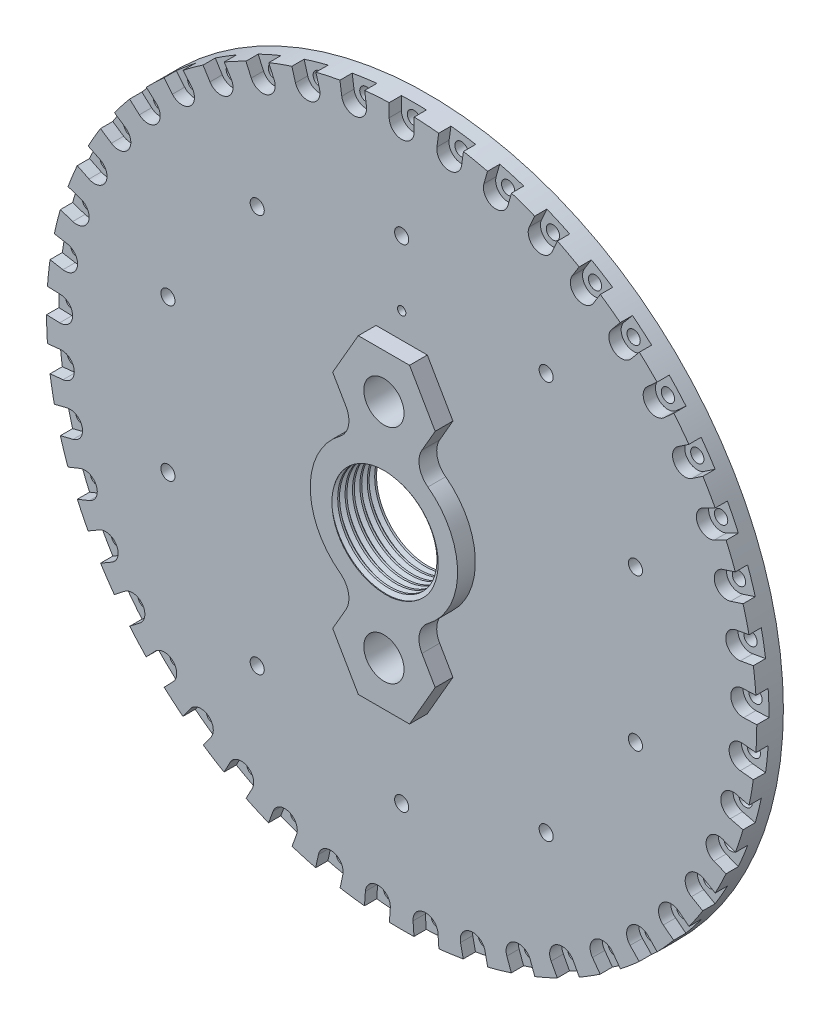
SolidWorks part; units mm, degrees
material "AISI 316 Stainless Steel Sheet (SS)"
ref_plane "Front Plane" through (0, 0, 0) normal (0, 0, 1) x (1, 0, 0)
ref_plane "Top Plane" through (0, 0, 0) normal (0, 1, 0) x (1, 0, 0)
ref_plane "Right Plane" through (0, 0, 0) normal (1, 0, 0) x (0, 0, -1)
sketch "Sketch1" plane through (0, 0, 0) normal (1, 0, 0) x (0, 0, -1)
  line L0 (0, 21.082) -> (0, 101.6)
  line L1 (0, 101.6) -> (7.62, 101.6)
  line L2 (7.62, 101.6) -> (7.62, 88.6333)
  line L3 (7.62, 83.82) -> (5.08, 83.82)
  line L4 (5.08, 83.82) -> (5.08, 56.8325)
  line L5 (5.08, 56.8325) -> (7.62, 56.8325)
  line L6 (7.62, 56.8325) -> (7.62, 53.0225)
  line L7 (7.62, 14.732) -> (-5.08, 14.732)
  line L8 (-5.08, 14.732) -> (-5.08, 21.082)
  line L9 (-5.08, 21.082) -> (0, 21.082)
  line L10 (0, 0) -> (59.2702, 0) construction
  line L12 (7.62, 49.6951) -> (6.2992, 49.6951)
  line L14 (7.62, 47.0535) -> (6.2992, 47.0535)
  line L15 (6.2992, 49.6951) -> (6.2992, 47.0535)
  line L20 (7.62, 47.0535) -> (7.62, 46.0375)
  line L21 (7.62, 85.1027) -> (7.62, 83.82)
  line L22 (7.62, 50.4825) -> (7.62, 49.6951)
  line L23 (7.62, 21.59) -> (7.62, 14.732)
  line L24 (7.62, 46.0375) -> (5.08, 46.0375)
  line L26 (7.62, 21.59) -> (5.08, 21.59)
  line L27 (5.08, 46.0375) -> (5.08, 21.59)
  line L28 (7.62, 53.0225) -> (6.35, 53.0225)
  line L32 (7.62, 50.4825) -> (6.35, 50.4825)
  line L33 (6.35, 53.0225) -> (6.35, 50.4825)
  line L35 (7.62, 88.6333) -> (5.6642, 88.6333)
  line L37 (7.62, 85.1027) -> (5.6642, 85.1027)
  line L38 (5.6642, 88.6333) -> (5.6642, 85.1027)
  point P19 (6.35, 51.7525)
  point P22 (6.2992, 48.3743)
  point P31 (5.6642, 86.868)
  dimension "D1" = 203.2
  dimension "D6" = 12.7
  dimension "D8" = 6.35
  dimension "D10" = 96.7486
  dimension "D9" = 2.6416
  dimension "D11" = 1.3208
  dimension "D7" = 29.464
  dimension "D4" = 2.54
  dimension "D14" = 43.18
  dimension "D2" = 2.54
  dimension "D3" = 7.62
  dimension "D12" = 167.64
  dimension "D5" = 113.665
  dimension "D13" = 92.075
  dimension "D15" = 1.27
  dimension "D16" = 2.54
  dimension "D17" = 103.505
  dimension "D18" = 1.9558
  dimension "D19" = 3.5306
  dimension "D20" = 173.736
revolve "Revolve1" add sketch "Sketch1" angle 360 about L10 region at (0, 56.7778, -2.7599)
thread "Thread1" pitch 2.1167 method cut profile "Thread Profile1" start angle 0, offset 4.318, length 0, pitch 2.1167, diameter 29.464
ref_plane "Plane1" through (-14.732, 0, 9.398) normal (0, -1, 0) x (-1, 0, 0)
sketch "Thread Profile1" plane through (-14.732, 0, 9.398) normal (0, -1, 0) x (-1, 0, 0)
  line L0 (0, 0) -> (0, 2.1167) construction
  line L1 (0, 0) -> (1.1457, 0.6615)
  line L2 (1.1457, 0.6615) -> (1.1457, 0.926)
  line L3 (1.1457, 0.926) -> (0, 1.5875)
  line L4 (1.1457, 0.7937) -> (0, 0.7937) construction
  line L11 (0, 0) -> (0, 1.5875)
  point P2 (0, 0)
  dimension "Pitch" = 2.1167
  dimension "Profile_Angle" = 60
  dimension "Profile_Land" = 0.2646
  dimension "Profile_Height" = 1.1457
sketch "Sketch15" plane through (0, 0, 0) normal (0, 0, 1) x (1, 0, 0)
  line L10 (0, 0) -> (104.8126, 0) construction
  line L11 (7.3323, 19.05) -> (14.6647, 31.75)
  line L12 (14.6647, 31.75) -> (7.3323, 44.45)
  line L13 (7.3323, 44.45) -> (-7.3323, 44.45)
  line L14 (-7.3323, 44.45) -> (-14.6647, 31.75)
  line L15 (-14.6647, 31.75) -> (-7.3323, 19.05)
  line L16 (-7.3323, 19.05) -> (7.3323, 19.05)
  line L17 (-7.3323, -19.05) -> (7.3323, -19.05)
  line L18 (-14.6647, -31.75) -> (-7.3323, -19.05)
  line L19 (-7.3323, -44.45) -> (-14.6647, -31.75)
  line L20 (7.3323, -44.45) -> (-7.3323, -44.45)
  line L21 (14.6647, -31.75) -> (7.3323, -44.45)
  line L22 (7.3323, -19.05) -> (14.6647, -31.75)
  circle A8 centre (0, 31.75) radius 12.7 construction
  circle A9 centre (0, -31.75) radius 12.7 construction
  dimension "D2" = 63.5
  dimension "D1" = 25.4
extrude "Boss-Extrude1" add sketch "Sketch15" along normal up to surface (5.08 mm away) up to face at (21.082, 0, 5.08)
hole_wizard "1/2-20 Tapped Hole2" positions "Sketch20" profile "Sketch17" tap size "1/2-20" standard "ANSI Inch" end condition through all
sketch "Sketch20" plane through (0, 0, 5.08) normal (0, 0, 1) x (1, 0, 0)
  point P9 (0, 31.75)
  point P16 (0, -31.75)
sketch "Sketch17" plane through (0, 31.75, 5.08) normal (1, 0, 0) x (0, -1, 0)
  line L0 (0, 0) -> (0, 13.4424)
  line L1 (0, 13.4424) -> (5.7544, 13.4424)
  line L2 (5.7544, 13.4424) -> (5.7544, 0)
  line L5 (5.7544, 0) -> (0, 0)
  line L11 (0, -6.35) -> (0, 107.95) construction
  dimension "Thru Tap Drill Dia." = 11.5087
  dimension "Thru Tap Drill Depth" = 13.4424
cosmetic thread "Hole Thread3" parameters "D2"=12.7
cosmetic thread "Hole Thread4" parameters "D2"=12.7
hole_wizard "CBORE for #6 Socket Head Cap Screw1" positions "Sketch31" profile "Sketch9" counterbore size "#6" standard "ANSI Inch" end condition up to next
sketch "Sketch31" [suppressed] plane through (0, 0, 0) normal (0, 0, 1) x (1, 0, 0)
  circle A0 centre (0, 0) radius 97.79 construction
  point P0 (0, 97.79)
  point P16 (13.6097, 96.8383)
  point P17 (26.9546, 94.0018)
  point P18 (39.7748, 89.3356)
  point P19 (51.8208, 82.9306)
  point P20 (62.8582, 74.9115)
  point P21 (72.6721, 65.4343)
  point P22 (81.0716, 54.6835)
  point P23 (87.8931, 42.8683)
  point P24 (93.0038, 30.2188)
  point P25 (96.3044, 16.9811)
  point P26 (97.7304, 3.4128)
  point P27 (97.2543, -10.2218)
  point P28 (94.8852, -23.6575)
  point P29 (90.6693, -36.6328)
  point P30 (84.6886, -48.895)
  point P31 (77.0596, -60.2055)
  point P32 (67.9306, -70.3442)
  point P33 (57.4795, -79.1138)
  point P34 (45.9096, -86.3434)
  point P35 (33.4461, -91.8925)
  point P36 (20.3317, -95.6531)
  point P37 (6.8215, -97.5518)
  point P38 (-6.8215, -97.5518)
  point P39 (-20.3317, -95.6531)
  point P40 (-33.4461, -91.8925)
  point P41 (-45.9096, -86.3434)
  point P42 (-57.4795, -79.1138)
  point P43 (-67.9306, -70.3442)
  point P44 (-77.0596, -60.2055)
  point P45 (-84.6886, -48.895)
  point P46 (-90.6693, -36.6328)
  point P47 (-94.8852, -23.6575)
  point P48 (-97.2543, -10.2218)
  point P49 (-97.7304, 3.4128)
  point P50 (-96.3044, 16.9811)
  point P51 (-93.0038, 30.2188)
  point P52 (-87.8931, 42.8683)
  point P53 (-81.0716, 54.6835)
  point P54 (-72.6721, 65.4343)
  point P55 (-62.8582, 74.9115)
  point P56 (-51.8208, 82.9306)
  point P57 (-39.7748, 89.3356)
  point P58 (-26.9546, 94.0018)
  point P59 (-13.6097, 96.8383)
  dimension "D1" = 195.58
  dimension "D2" = 45
sketch "Sketch9" plane through (0, 97.79, 0) normal (1, 0, 0) x (0, -1, 0)
  line L0 (0, 0) -> (0, 7.62)
  line L1 (0, 7.62) -> (1.8986, 7.62)
  line L3 (1.8986, 7.62) -> (1.8986, 3.5052)
  line L4 (1.8986, 3.5052) -> (3.5725, 3.5052)
  line L5 (3.5725, 3.5052) -> (3.5725, 0)
  line L7 (3.5725, 0) -> (0, 0)
  line L11 (0, -6.35) -> (0, 107.95) construction
  dimension "Thru Hole Dia." = 3.7973
  dimension "Thru Hole Depth" = 7.62
  dimension "C'Bore Dia." = 7.145
  dimension "C'Bore Depth" = 3.5052
sketch "Sketch29" plane through (0, 0, 0) normal (0, 0, 1) x (1, 0, 0)
  line L0 (3.5725, 97.79) -> (3.5725, 101.5372)
  line L1 (-3.5725, 97.79) -> (-3.5725, 101.5372)
  line L2 (17.1475, 96.3411) -> (17.669, 100.0518)
  line L3 (10.072, 97.3355) -> (10.5935, 101.0462)
  line L4 (30.3887, 93.0171) -> (31.4216, 96.6191)
  line L5 (23.5205, 94.9865) -> (24.5533, 98.5885)
  line L6 (43.0384, 87.8825) -> (44.5625, 91.3058)
  line L7 (36.5111, 90.7887) -> (38.0352, 94.2119)
  line L8 (54.8505, 81.0375) -> (56.8362, 84.2153)
  line L9 (48.7911, 84.8238) -> (50.7768, 88.0015)
  line L10 (65.5949, 72.6151) -> (68.0035, 75.4856)
  line L11 (60.1215, 77.2079) -> (62.5301, 80.0784)
  line L12 (75.0626, 62.7794) -> (77.8473, 65.2867)
  line L13 (70.2817, 68.0892) -> (73.0663, 70.5965)
  line L14 (83.0693, 51.7217) -> (86.1759, 53.8171)
  line L15 (79.0739, 57.6452) -> (82.1804, 59.7406)
  line L16 (89.4592, 39.6574) -> (92.8271, 41.3)
  line L17 (86.327, 46.0793) -> (89.6949, 47.7219)
  line L18 (94.1078, 26.8211) -> (97.6716, 27.9791)
  line L19 (91.8999, 33.6164) -> (95.4636, 34.7744)
  line L20 (96.9247, 13.4628) -> (100.615, 14.1135)
  line L21 (95.684, 20.4993) -> (99.3742, 21.15)
  line L22 (97.8551, -0.1575) -> (101.6, -0.0267)
  line L23 (97.6058, 6.9832) -> (101.3506, 7.1139)
  line L24 (96.8809, -13.7748) -> (100.6075, -14.1665)
  line L25 (97.6277, -6.6689) -> (101.3544, -7.0606)
  line L26 (94.021, -27.1239) -> (97.6568, -28.0305)
  line L27 (95.7495, -20.1912) -> (99.3854, -21.0977)
  line L28 (89.331, -39.9452) -> (92.8053, -41.3489)
  line L29 (92.0076, -33.3204) -> (95.4819, -34.7241)
  line L30 (82.9024, -51.9889) -> (86.1475, -53.8625)
  line L31 (86.4749, -45.8011) -> (89.72, -47.6747)
  line L32 (74.8601, -63.0207) -> (77.8129, -65.3277)
  line L33 (79.259, -57.3904) -> (82.2118, -59.6973)
  line L34 (65.3608, -72.8259) -> (67.9638, -75.5214)
  line L35 (70.5005, -67.8626) -> (73.1035, -70.5581)
  line L36 (54.5893, -81.2136) -> (56.7918, -84.2452)
  line L37 (60.3697, -77.0139) -> (62.5723, -80.0454)
  line L38 (42.7553, -88.0206) -> (44.5145, -91.3292)
  line L39 (49.064, -84.6663) -> (50.8232, -87.9748)
  line L40 (30.0891, -93.1144) -> (31.3707, -96.6356)
  line L41 (36.8032, -90.6707) -> (38.0848, -94.1919)
  line L42 (16.8372, -96.3958) -> (17.6163, -100.0611)
  line L43 (23.8261, -94.9103) -> (24.6052, -98.5756)
  line L44 (3.2577, -97.801) -> (3.5191, -101.539)
  line L45 (10.3853, -97.3026) -> (10.6467, -101.0406)
  line L46 (-10.3853, -97.3026) -> (-10.6467, -101.0406)
  line L47 (-3.2577, -97.801) -> (-3.5191, -101.539)
  line L48 (-23.8261, -94.9103) -> (-24.6052, -98.5756)
  line L49 (-16.8372, -96.3958) -> (-17.6163, -100.0611)
  line L50 (-36.8032, -90.6707) -> (-38.0848, -94.1919)
  line L51 (-30.0891, -93.1144) -> (-31.3707, -96.6356)
  line L52 (-49.064, -84.6663) -> (-50.8232, -87.9748)
  line L53 (-42.7553, -88.0206) -> (-44.5145, -91.3292)
  line L54 (-60.3697, -77.0139) -> (-62.5723, -80.0454)
  line L55 (-54.5893, -81.2136) -> (-56.7918, -84.2452)
  line L56 (-70.5005, -67.8626) -> (-73.1035, -70.5581)
  line L57 (-65.3608, -72.8259) -> (-67.9638, -75.5214)
  line L58 (-79.259, -57.3904) -> (-82.2118, -59.6973)
  line L59 (-74.8601, -63.0207) -> (-77.8129, -65.3277)
  line L60 (-86.4749, -45.8011) -> (-89.72, -47.6747)
  line L61 (-82.9024, -51.9889) -> (-86.1475, -53.8625)
  line L62 (-92.0076, -33.3204) -> (-95.4819, -34.7241)
  line L63 (-89.331, -39.9452) -> (-92.8053, -41.3489)
  line L64 (-95.7495, -20.1912) -> (-99.3854, -21.0977)
  line L65 (-94.021, -27.1239) -> (-97.6568, -28.0305)
  line L66 (-97.6277, -6.6689) -> (-101.3544, -7.0606)
  line L67 (-96.8809, -13.7748) -> (-100.6075, -14.1665)
  line L68 (-97.6058, 6.9832) -> (-101.3506, 7.1139)
  line L69 (-97.8551, -0.1575) -> (-101.6, -0.0267)
  line L70 (-95.684, 20.4993) -> (-99.3742, 21.15)
  line L71 (-96.9247, 13.4628) -> (-100.615, 14.1135)
  line L72 (-91.8999, 33.6164) -> (-95.4636, 34.7744)
  line L73 (-94.1078, 26.8211) -> (-97.6716, 27.9791)
  line L74 (-86.327, 46.0793) -> (-89.6949, 47.7219)
  line L75 (-89.4592, 39.6574) -> (-92.8271, 41.3)
  line L76 (-79.0739, 57.6452) -> (-82.1804, 59.7406)
  line L77 (-83.0693, 51.7217) -> (-86.1759, 53.8171)
  line L78 (-70.2817, 68.0892) -> (-73.0663, 70.5965)
  line L79 (-75.0626, 62.7794) -> (-77.8473, 65.2867)
  line L80 (-60.1215, 77.2079) -> (-62.5301, 80.0784)
  line L81 (-65.5949, 72.6151) -> (-68.0035, 75.4856)
  line L82 (-48.7911, 84.8238) -> (-50.7768, 88.0015)
  line L83 (-54.8505, 81.0375) -> (-56.8362, 84.2153)
  line L84 (-36.5111, 90.7887) -> (-38.0352, 94.2119)
  line L85 (-43.0384, 87.8825) -> (-44.5625, 91.3058)
  line L86 (-23.5205, 94.9865) -> (-24.5533, 98.5885)
  line L87 (-30.3887, 93.0171) -> (-31.4216, 96.6191)
  line L88 (-10.072, 97.3355) -> (-10.5935, 101.0462)
  line L89 (-17.1475, 96.3411) -> (-17.669, 100.0518)
  circle A0 centre (0, 97.79) radius 3.5725 construction
  circle A1 centre (0, 0) radius 101.6 construction
  circle A2 centre (13.6097, 96.8383) radius 3.5725
  circle A3 centre (0, 97.79) radius 3.5725
  circle A4 centre (26.9546, 94.0018) radius 3.5725
  circle A5 centre (0, 0) radius 101.6
  circle A7 centre (39.7748, 89.3356) radius 3.5725
  circle A8 centre (51.8208, 82.9306) radius 3.5725
  circle A9 centre (62.8582, 74.9115) radius 3.5725
  circle A10 centre (72.6721, 65.4343) radius 3.5725
  circle A11 centre (81.0716, 54.6835) radius 3.5725
  circle A12 centre (87.8931, 42.8683) radius 3.5725
  circle A13 centre (93.0038, 30.2188) radius 3.5725
  circle A14 centre (96.3044, 16.9811) radius 3.5725
  circle A15 centre (97.7304, 3.4128) radius 3.5725
  circle A16 centre (97.2543, -10.2218) radius 3.5725
  circle A17 centre (94.8852, -23.6575) radius 3.5725
  circle A18 centre (90.6693, -36.6328) radius 3.5725
  circle A19 centre (84.6886, -48.895) radius 3.5725
  circle A20 centre (77.0596, -60.2055) radius 3.5725
  circle A21 centre (67.9306, -70.3442) radius 3.5725
  circle A22 centre (57.4795, -79.1138) radius 3.5725
  circle A23 centre (45.9096, -86.3434) radius 3.5725
  circle A24 centre (33.4461, -91.8925) radius 3.5725
  circle A25 centre (13.6097, 96.8383) radius 1.8986 construction
  circle A26 centre (20.3317, -95.6531) radius 3.5725
  circle A27 centre (6.8215, -97.5518) radius 3.5725
  circle A28 centre (-6.8215, -97.5518) radius 3.5725
  circle A29 centre (-20.3317, -95.6531) radius 3.5725
  circle A30 centre (-33.4461, -91.8925) radius 3.5725
  circle A31 centre (-45.9096, -86.3434) radius 3.5725
  circle A32 centre (-57.4795, -79.1138) radius 3.5725
  circle A33 centre (-67.9306, -70.3442) radius 3.5725
  circle A34 centre (-77.0596, -60.2055) radius 3.5725
  circle A35 centre (-84.6886, -48.895) radius 3.5725
  circle A36 centre (-90.6693, -36.6328) radius 3.5725
  circle A37 centre (-94.8852, -23.6575) radius 3.5725
  circle A38 centre (-97.2543, -10.2218) radius 3.5725
  circle A39 centre (-97.7304, 3.4128) radius 3.5725
  circle A40 centre (-96.3044, 16.9811) radius 3.5725
  circle A41 centre (-93.0038, 30.2188) radius 3.5725
  circle A42 centre (-87.8931, 42.8683) radius 3.5725
  circle A43 centre (-81.0716, 54.6835) radius 3.5725
  circle A44 centre (-72.6721, 65.4343) radius 3.5725
  circle A45 centre (-62.8582, 74.9115) radius 3.5725
  circle A46 centre (-51.8208, 82.9306) radius 3.5725
  circle A47 centre (-39.7748, 89.3356) radius 3.5725
  circle A48 centre (-26.9546, 94.0018) radius 3.5725
  circle A49 centre (-13.6097, 96.8383) radius 3.5725
  circle A51 centre (0, 0) radius 101.6
  point P129 (0, 0)
  dimension "D2" = 45
extrude "Cut-Extrude1" cut sketch "Sketch29" against normal up to surface (3.5052 mm away) contours L1 L0 region at (0, 101.4435, 0) up to face at (1.8986, 97.79, -3.5052)
pattern_circular "CirPattern2" count 45 over 360 about axis through (0, 0, 0) along (0, 0, 1) of "Cut-Extrude1"
fillet "Fillet1" radius 6.35 4 edges at (-7.6711, 19.6368, 2.54) (-7.6711, -19.6368, 2.54) (7.6711, -19.6368, 2.54) (7.6711, 19.6368, 2.54)
hole_wizard "3/32 (0.09375) Dowel Hole1" positions "Sketch23" profile "Sketch22" hole size "3/32" standard "ANSI Inch" end condition up to next
sketch "Sketch23" plane through (0, 0, -6.35) normal (0, 0, -1) x (-1, 0, 0)
  line L0 (0, 50.4825) -> (0, 53.0225) construction
  circle A1 centre (0, 0) radius 50.4825 construction
  circle A2 centre (0, 0) radius 53.0225 construction
  point P0 (0, 51.7525)
  point P15 (0, 51.7525)
sketch "Sketch22" plane through (0, 51.7525, -6.35) normal (1, 0, 0) x (0, 1, 0)
  line L0 (0, 0) -> (0, 6.35)
  line L1 (0, 6.35) -> (1.1906, 6.35)
  line L2 (1.1906, 6.35) -> (1.1906, 0)
  line L5 (1.1906, 0) -> (0, 0)
  line L11 (0, -6.35) -> (0, 107.95) construction
  dimension "Thru Hole Dia." = 2.3812
  dimension "Thru Hole Depth" = 6.35
sketch "Sketch24" plane through (0, 0, 0) normal (0, 0, 1) x (1, 0, 0)
  line L0 (0, 56.8325) -> (0, 83.82) construction
  line L2 (6.8215, 97.5518) -> (0, 0) construction
  circle A0 centre (0, 0) radius 70.3263 construction
  circle A1 centre (0, 0) radius 56.8325 construction
  circle A2 centre (0, 0) radius 56.8325 construction
  circle A3 centre (0, 0) radius 83.82 construction
  arc A4 (0, 97.79) -> (13.6097, 96.8383) centre (0, 0) cw construction
  arc A6 (10.072, 97.3355) -> (17.1475, 96.3411) centre (13.6097, 96.8383) ccw construction
  point P0 (0, 70.3263)
  point P14 (0, 70.3263)
sketch "Sketch25" plane through (0, 0, 0) normal (0, 0, 1) x (1, 0, 0)
  point P0 (0, 70.3263)
hole_wizard "#10-32 Tapped Hole1" positions "Sketch25" profile "Sketch27" tap size "#10-32" standard "ANSI Inch"
sketch "Sketch27" plane through (0, 70.3263, 0) normal (1, 0, 0) x (0, -1, 0)
  line L0 (0, 0) -> (0, 4.318)
  line L1 (0, 4.318) -> (2.0193, 3.1047)
  line L2 (2.0193, 3.1047) -> (2.0193, 0)
  line L5 (2.0193, 0) -> (0, 0)
  line L10 (0, 4.318) -> (-2.0193, 3.1047) construction
  line L11 (0, -6.35) -> (0, 107.95) construction
  dimension "Tap Drill Dia." = 4.0386
  dimension "Tap Drill Depth" = 4.318
  dimension "Drill Angle" = 118
cosmetic thread "Hole Thread5" parameters "D1"=9.652, "D2"=4.826
pattern_circular "CirPattern1" count 10 over 360 about axis through (0, 0, 0) along (0, 0, 1) of "#10-32 Tapped Hole1" reverse direction yes
cosmetic thread "Hole Thread6" parameters "D1"=9.652, "D2"=4.826
cosmetic thread "Hole Thread7" parameters "D1"=9.652, "D2"=4.826
cosmetic thread "Hole Thread8" parameters "D1"=9.652, "D2"=4.826
cosmetic thread "Hole Thread9" parameters "D1"=9.652, "D2"=4.826
cosmetic thread "Hole Thread10" parameters "D1"=9.652, "D2"=4.826
cosmetic thread "Hole Thread11" parameters "D1"=9.652, "D2"=4.826
cosmetic thread "Hole Thread12" parameters "D1"=9.652, "D2"=4.826
cosmetic thread "Hole Thread13" parameters "D1"=9.652, "D2"=4.826
cosmetic thread "Hole Thread14" parameters "D1"=9.652, "D2"=4.826
equation "\"numBolts\"= 45"
equation "\"chamberOD\" = 8"
equation "\"boltDia\" = 7.7"
equation "\"D1@Sketch1\"=\"chamberOD\""
equation "\"D1@Sketch31\" = \"boltDia\""
equation "\"D2@Sketch31\" = \"numBolts\""
equation "\"D2@Sketch29\"=\"numBolts\""
equation "\"D1@CirPattern2\"=\"numBolts\""
